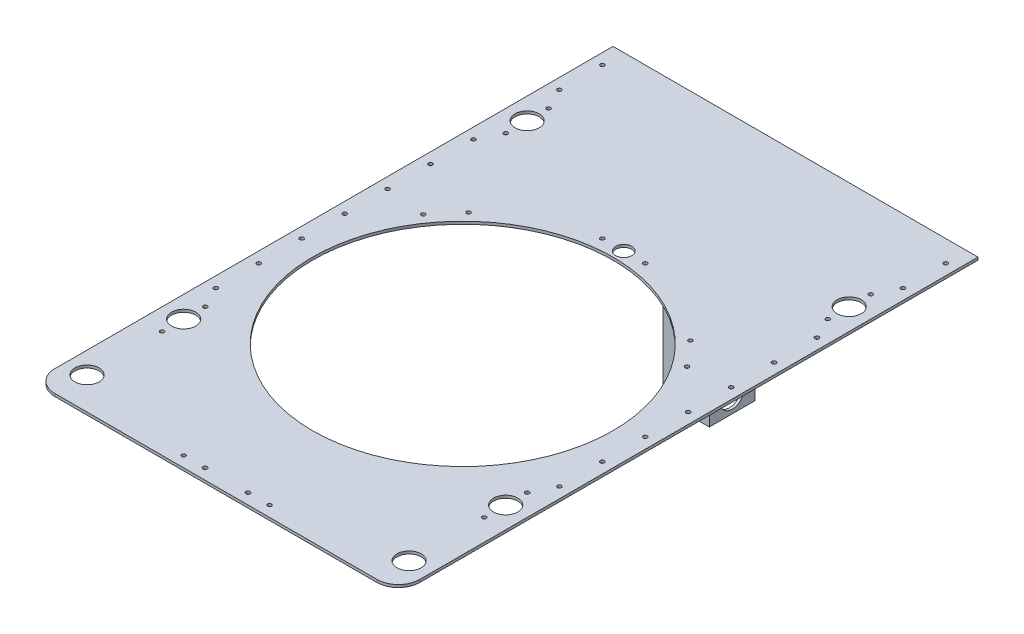
SolidWorks part; units mm, degrees
ref_plane "Front Plane" through (0, 0, 0) normal (0, 0, 1) x (1, 0, 0)
ref_plane "Top Plane" through (0, 0, 0) normal (0, 1, 0) x (1, 0, 0)
ref_plane "Right Plane" through (0, 0, 0) normal (1, 0, 0) x (0, 0, -1)
sketch "Sketch1" plane through (0, 0, 0) normal (0, 1, 0) x (1, 0, 0)
  line L1 (-215.9, 342.9) -> (215.9, 342.9)
  line L2 (-215.9, 342.9) -> (-215.9, -342.9)
  line L3 (-215.9, -342.9) -> (215.9, -342.9)
  line L4 (215.9, 342.9) -> (215.9, -342.9)
  line L5 (-215.9, 342.9) -> (215.9, -342.9) construction
  line L6 (-215.9, -342.9) -> (215.9, 342.9) construction
  point P0 (0, 0)
  dimension "D1" = 431.8
  dimension "D2" = 685.8
extrude "Boss-Extrude1" add sketch "Sketch1" along normal blind 3.175
sketch "Sketch2" plane through (0, 3.175, 0) normal (0, 1, 0) x (1, 0, 0)
  line L0 (0, -342.9) -> (0, 342.9) construction
  line L1 (-215.9, -342.9) -> (215.9, -342.9) construction
  line L2 (215.9, 342.9) -> (-215.9, 342.9) construction
  line L3 (-215.9, 342.9) -> (-215.9, -342.9) construction
  circle A0 centre (-190.5, -304.8) radius 14.3129
  circle A1 centre (-190.5, -190.5) radius 14.3129
  circle A2 centre (190.5, -304.8) radius 14.3129
  circle A3 centre (190.5, -190.5) radius 14.3129
  circle A4 centre (190.5, -190.5) radius 25.4 construction
  circle A5 centre (-190.5, -190.5) radius 25.4 construction
  circle A6 centre (190.5, -215.9) radius 2.3813
  circle A7 centre (190.5, -165.1) radius 2.3813
  circle A8 centre (-190.5, -215.9) radius 2.3813
  circle A9 centre (-190.5, -165.1) radius 2.3813
  dimension "D1" = 28.6258
  dimension "D2" = 28.6258
  dimension "D6" = 50.8
  dimension "D7" = 50.8
  dimension "D8" = 4.7625
  dimension "D9" = 4.7625
  dimension "D10" = 4.7625
  dimension "D11" = 4.7625
  dimension "D3" = 38.1
  dimension "D4" = 114.3
  dimension "D5" = 25.4
extrude "Cut-Extrude1" cut sketch "Sketch2" against normal through all
sketch "Sketch3" plane through (0, 0, 0) normal (0, -1, 0) x (-1, 0, 0)
  line L1 (29.8706, 270.2084) -> (-24.7394, 270.2084)
  line L2 (29.8706, 270.2084) -> (29.8706, 216.2334)
  line L3 (29.8706, 216.2334) -> (-24.7394, 216.2334)
  line L4 (-24.7394, 270.2084) -> (-24.7394, 216.2334)
  line L5 (29.8706, 270.2084) -> (-24.7394, 216.2334) construction
  line L6 (29.8706, 216.2334) -> (-24.7394, 270.2084) construction
  point P0 (2.5656, 243.2209)
  dimension "D1" = 53.975
  dimension "D2" = 54.61
extrude "Boss-Extrude2" add sketch "Sketch3" along normal blind 203.2
fillet "Fillet1" radius 20.32 4 edges at (24.7394, 0, -243.2209) (-2.5656, 0, -270.2084) (-2.5656, 0, -216.2334) (-29.8706, 0, -243.2209)
sketch "Sketch4" plane through (0, -203.2, 0) normal (0, -1, 0) x (-1, 0, 0)
  line L0 (-24.7394, 216.2334) -> (29.8706, 216.2334) construction
  line L1 (26.6956, 267.0334) -> (-21.5644, 267.0334)
  line L2 (26.6956, 267.0334) -> (26.6956, 219.4084)
  line L3 (26.6956, 219.4084) -> (-21.5644, 219.4084)
  line L4 (-21.5644, 267.0334) -> (-21.5644, 219.4084)
  line L5 (26.6956, 267.0334) -> (-21.5644, 219.4084) construction
  line L6 (26.6956, 219.4084) -> (-21.5644, 267.0334) construction
  line L7 (29.8706, 270.2084) -> (-24.7394, 270.2084) construction
  line L8 (29.8706, 216.2334) -> (29.8706, 270.2084) construction
  line L9 (-24.7394, 270.2084) -> (-24.7394, 216.2334) construction
  point P0 (2.5656, 243.2209)
  dimension "D1" = 3.175
  dimension "D2" = 3.175
  dimension "D3" = 3.175
  dimension "D4" = 3.175
extrude "Cut-Extrude2" cut sketch "Sketch4" against normal blind 203.2
sketch "Sketch5" plane through (-29.8706, 0, 0) normal (-1, 0, 0) x (0, 0, 1)
  line L0 (-216.2334, -203.2) -> (-216.2334, -20.32) construction
  line L1 (-216.2334, -203.2) -> (-270.2084, -203.2) construction
  circle A0 centre (-243.2209, -184.15) radius 14.2875
  dimension "D1" = 28.575
  dimension "D2" = 26.9875
  dimension "D3" = 19.05
extrude "Cut-Extrude3" cut sketch "Sketch5" against normal blind 203.2
sketch "Sketch6" plane through (0, 3.175, 0) normal (0, 1, 0) x (1, 0, 0)
  circle A0 centre (0, -50.8) radius 177.8
  dimension "D1" = 355.6
  dimension "D2" = 50.8
extrude "Cut-Extrude4" cut sketch "Sketch6" against normal through all
sketch "Sketch8" plane through (0, 3.175, 0) normal (0, 1, 0) x (1, 0, 0)
  circle A0 centre (0, 139.7) radius 9.525
  circle A2 centre (0, 139.7) radius 25.4 construction
  circle A3 centre (25.4, 139.7) radius 2.3813
  circle A4 centre (-25.4, 139.7) radius 2.3813
  dimension "D1" = 19.05
  dimension "D3" = 50.8
  dimension "D4" = 4.7625
  dimension "D5" = 4.7625
  dimension "D2" = 139.7
extrude "Cut-Extrude6" cut sketch "Sketch8" against normal through all
fillet "Fillet2" radius 25.4 2 edges at (215.9, 1.5875, 342.9) (-215.9, 1.5875, 342.9)
sketch "Sketch10" plane through (0, 3.175, 0) normal (0, 1, 0) x (1, 0, 0)
  line L0 (-215.9, 342.9) -> (-215.9, -317.5) construction
  line L1 (215.9, -317.5) -> (215.9, 342.9) construction
  circle A0 centre (-190.5, 215.9) radius 14.3129
  circle A1 centre (190.5, 215.9) radius 14.3129
  circle A2 centre (-190.5, 215.9) radius 25.4 construction
  circle A3 centre (190.5, 215.9) radius 25.4 construction
  circle A4 centre (190.5, 190.5) radius 2.3813
  circle A5 centre (190.5, 241.3) radius 2.3813
  circle A6 centre (-190.5, 190.5) radius 2.3813
  circle A7 centre (-190.5, 241.3) radius 2.3813
  circle A8 centre (190.5, -190.5) radius 14.3129 construction
  circle A9 centre (-190.5, -190.5) radius 14.3129 construction
  point P14 (0, 0)
  point P15 (-190.3345, 226.462)
  dimension "D1" = 28.6258
  dimension "D2" = 50.8
  dimension "D3" = 28.6258
  dimension "D4" = 50.8
  dimension "D5" = 4.7625
  dimension "D6" = 4.7625
  dimension "D7" = 4.7625
  dimension "D8" = 4.7625
  dimension "D9" = 25.4
  dimension "D10" = 25.4
  dimension "D11" = 406.4
  dimension "D12" = 406.4
extrude "Cut-Extrude8" cut sketch "Sketch10" against normal through all
sketch "Sketch11" plane through (0, 3.175, 0) normal (0, 1, 0) x (1, 0, 0)
  line L0 (0, -50.8) -> (156.0485, 58.4663) construction
  line L6 (0, 0) -> (0, 139.7) construction
  circle A0 centre (0, -50.8) radius 177.8
  circle A1 centre (0, -50.8) radius 177.8 construction
  circle A2 centre (0, -50.8) radius 184.15
  circle A3 centre (0, -50.8) radius 215.9
  circle A4 centre (156.0485, 58.4663) radius 2.3813
  circle A5 centre (131.1838, 87.3342) radius 2.3813
  circle A6 centre (0, -50.8) radius 190.5 construction
  circle A7 centre (-131.1838, 87.3342) radius 2.3813
  circle A8 centre (-156.0485, 58.4663) radius 2.3813
  dimension "D1" = 368.3
  dimension "D6" = 431.8
  dimension "D7" = 381
  dimension "D9" = 4.7625
  dimension "D10" = 4.7625
  dimension "D2" = 55
  dimension "D8" = 38.1
extrude "Cut-Extrude9" cut sketch "Sketch11" against normal through all contours A4 | A5 | A7 | A8 region at (156.0485, 3.175, -58.4663) region at (131.1838, 3.175, -87.3342) region at (-131.1838, 3.175, -87.3342) region at (-156.0485, 3.175, -58.4663)
sketch "Sketch13" plane through (0, 3.175, 0) normal (0, 1, 0) x (1, 0, 0)
  line L0 (-215.9, 342.9) -> (-215.9, -317.5) construction
  line L1 (215.9, 342.9) -> (-215.9, 342.9) construction
  line L2 (0, -342.9) -> (0, 342.9) construction
  line L3 (-190.5, -342.9) -> (190.5, -342.9) construction
  circle A0 centre (-203.2, 317.5) radius 2.3813
  circle A1 centre (-203.2, 266.7) radius 2.3813
  circle A2 centre (-203.2, 215.9) radius 2.3813 [skipped]
  circle A3 centre (-203.2, 165.1) radius 2.3813
  circle A4 centre (-203.2, 114.3) radius 2.3813
  circle A5 centre (-203.2, 63.5) radius 2.3813
  circle A6 centre (-203.2, 12.7) radius 2.3813
  circle A7 centre (-203.2, -38.1) radius 2.3813
  circle A8 centre (-203.2, -88.9) radius 2.3813
  circle A9 centre (-203.2, -139.7) radius 2.3813
  circle A10 centre (203.2, -139.7) radius 2.3813
  circle A11 centre (203.2, 12.7) radius 2.3813
  circle A12 centre (203.2, 63.5) radius 2.3813
  circle A13 centre (203.2, 114.3) radius 2.3813
  circle A14 centre (203.2, 165.1) radius 2.3813
  circle A15 centre (203.2, 266.7) radius 2.3813
  circle A16 centre (203.2, 317.5) radius 2.3813
  circle A17 centre (-25.4, -330.2) radius 2.4664
  circle A20 centre (-50.8, -330.2) radius 2.3078
  circle A21 centre (50.8, -330.2) radius 2.3078
  circle A22 centre (25.4, -330.2) radius 2.4664
  circle A23 centre (203.2, -88.9) radius 2.3813
  circle A24 centre (203.2, -38.1) radius 2.3813
  point P50 (0, 0)
  dimension "D1" = 4.7625
  dimension "D2" = 12.7
  dimension "D3" = 25.4
  dimension "D5" = 25.4
  dimension "D6" = 50.8
  dimension "D7" = 12.7
  dimension "D8" = 12.7
  dimension "D4" = 10
extrude "Cut-Extrude10" cut sketch "Sketch13" against normal through all
